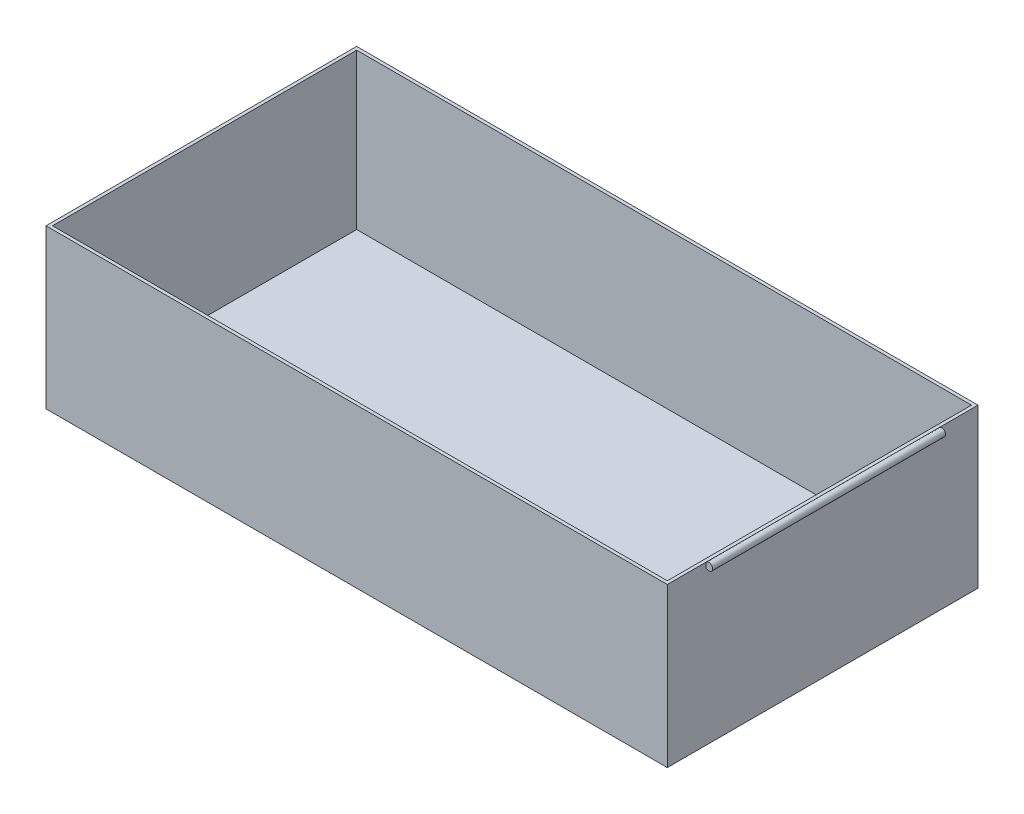
SolidWorks part; units mm, degrees
material "ASTM A36 Steel"
ref_plane "Front Plane" through (0, 0, 0) normal (0, 0, 1) x (1, 0, 0)
ref_plane "Top Plane" through (0, 0, 0) normal (0, 1, 0) x (1, 0, 0)
ref_plane "Right Plane" through (0, 0, 0) normal (1, 0, 0) x (0, 0, -1)
sketch "Sketch1" plane through (0, 0, 0) normal (0, 1, 0) x (1, 0, 0)
  line L1 (152.4, 76.2) -> (-152.4, 76.2)
  line L2 (152.4, 76.2) -> (152.4, -76.2)
  line L3 (152.4, -76.2) -> (-152.4, -76.2)
  line L4 (-152.4, 76.2) -> (-152.4, -76.2)
  line L5 (152.4, 76.2) -> (-152.4, -76.2) construction
  line L6 (152.4, -76.2) -> (-152.4, 76.2) construction
  point P0 (0, 0)
  dimension "D1" = 152.4
  dimension "D2" = 304.8
extrude "Boss-Extrude1" add sketch "Sketch1" along normal blind 1.5875
sketch "Sketch2" plane through (0, 1.5875, 0) normal (0, 1, 0) x (1, 0, 0)
  line L8 (-150.8125, 74.6125) -> (-150.8125, -74.6125)
  line L9 (-150.8125, -74.6125) -> (150.8125, -74.6125)
  line L10 (150.8125, -74.6125) -> (150.8125, 74.6125)
  line L11 (150.8125, 74.6125) -> (-150.8125, 74.6125)
  line L12 (-150.8125, 74.6125) -> (-150.8125, -74.6125)
  line L13 (-150.8125, -74.6125) -> (150.8125, -74.6125)
  line L14 (150.8125, -74.6125) -> (150.8125, 74.6125)
  line L15 (150.8125, 74.6125) -> (-150.8125, 74.6125)
  line L16 (-152.4, 76.2) -> (-152.4, -76.2)
  line L17 (-152.4, -76.2) -> (152.4, -76.2)
  line L18 (152.4, -76.2) -> (152.4, 76.2)
  line L19 (152.4, 76.2) -> (-152.4, 76.2)
  line L20 (-152.4, 76.2) -> (-152.4, -76.2)
  line L21 (-152.4, -76.2) -> (152.4, -76.2)
  line L22 (152.4, -76.2) -> (152.4, 76.2)
  line L23 (152.4, 76.2) -> (-152.4, 76.2)
  dimension "D1" = 1.5875
  dimension "D2" = 0
extrude "Boss-Extrude2" add sketch "Sketch2" along normal blind 76.2
sketch "Sketch3" plane through (0, 0, 0) normal (0, 0, 1) x (1, 0, 0)
  line L0 (152.4, 77.7875) -> (152.4, 0) construction
  line L1 (152.4, 77.7875) -> (152.4, 0)
  arc A0 (152.4, 77.7875) -> (152.4, 75.18) centre (153.7037, 76.4838) cw
  dimension "D1" = 1.8438
  dimension "D2" = 1.3037
extrude "Boss-Extrude3" add sketch "Sketch3" along normal mid plane 114.3 contours A0 L1 region at (153.8559, 76.4838, 0)
